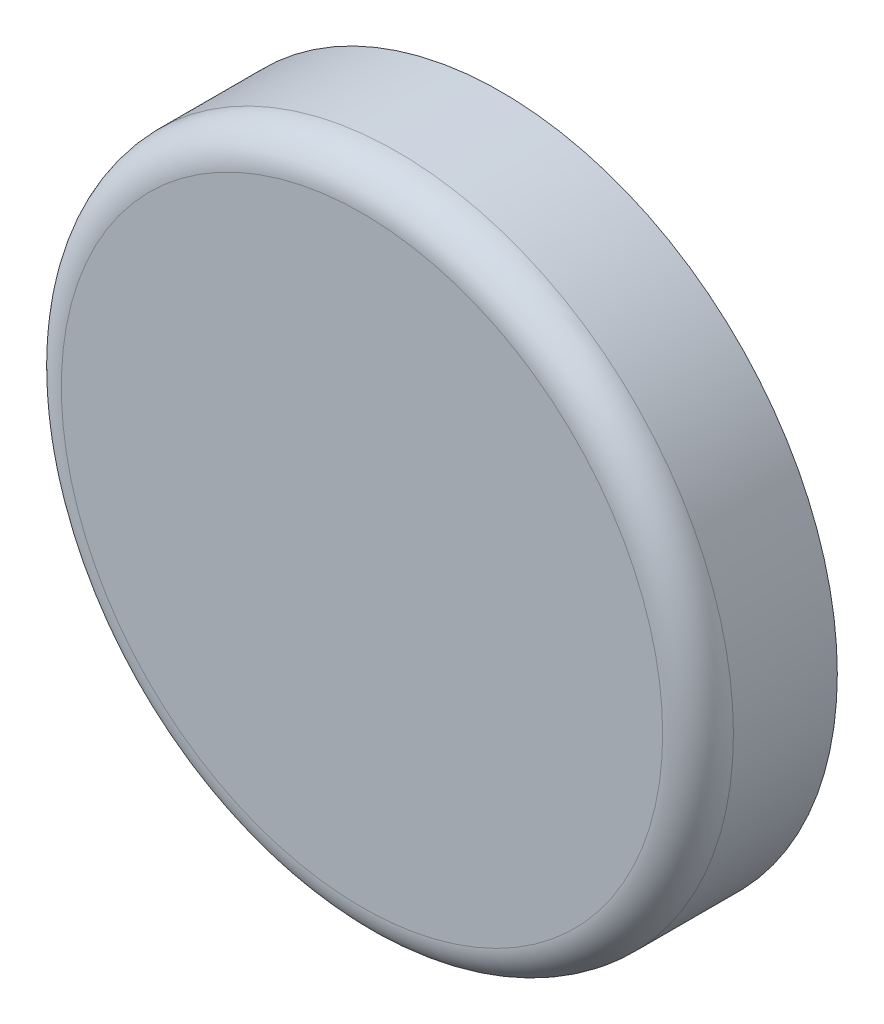
SolidWorks part; units mm, degrees
ref_plane "Front Plane" through (0, 0, 0) normal (0, 0, 1) x (1, 0, 0)
ref_plane "Top Plane" through (0, 0, 0) normal (0, 1, 0) x (1, 0, 0)
ref_plane "Right Plane" through (0, 0, 0) normal (1, 0, 0) x (0, 0, -1)
sketch "Sketch1" plane through (0, 0, 0) normal (0, 0, 1) x (1, 0, 0)
  circle A0 centre (0, 0) radius 12.065
  dimension "D1" = 24.13
extrude "Boss-Extrude1" add sketch "Sketch1" along normal blind 5
fillet "Fillet1" radius 1.27 1 edges at (12.065, 0, 5)
sketch "Sketch2" plane through (0, 0, 0) normal (0, 0, -1) x (-1, 0, 0)
  line L0 (0, 12.065) -> (0, -12.065) construction
  line L1 (-3.1, -3.1) -> (3.1, -3.1) construction
  line L2 (-3.1, -3.1) -> (-3.1, 3.1) construction
  line L3 (-3.1, 3.1) -> (3.1, 3.1) construction
  line L4 (3.1, -3.1) -> (3.1, 3.1) construction
  line L5 (-3.1, -3.1) -> (3.1, 3.1) construction
  line L6 (-3.1, 3.1) -> (3.1, -3.1) construction
  line L7 (-12.065, 0) -> (12.065, 0) construction
  line L8 (3.1, 2.084) -> (4.116, 2.084)
  line L9 (-2.084, 3.1) -> (2.084, 3.1)
  line L10 (-2.084, 3.1) -> (-2.084, 4.116)
  line L11 (-2.084, 4.116) -> (2.084, 4.116)
  line L12 (2.084, 3.1) -> (2.084, 4.116)
  line L13 (3.1, 2.084) -> (3.1, -2.084)
  line L14 (3.1, -2.084) -> (4.116, -2.084)
  line L15 (4.116, 2.084) -> (4.116, -2.084)
  line L16 (2.084, -3.1) -> (2.084, -4.116)
  line L17 (2.084, -3.1) -> (-2.084, -3.1)
  line L18 (-2.084, -3.1) -> (-2.084, -4.116)
  line L19 (2.084, -4.116) -> (-2.084, -4.116)
  line L20 (-3.1, -2.084) -> (-4.116, -2.084)
  line L21 (-3.1, -2.084) -> (-3.1, 2.084)
  line L22 (-3.1, 2.084) -> (-4.116, 2.084)
  line L23 (-4.116, -2.084) -> (-4.116, 2.084)
  circle A0 centre (0, 0) radius 12.065 construction
  point P0 (0, 0)
  point P18 (0, 4.116)
  point P33 (0, 0)
  dimension "D2" = 6.2
  dimension "D3" = 1.016
  dimension "D4" = 1.016
  dimension "D5" = 4
extrude "Boss-Extrude2" add sketch "Sketch2" along normal blind 1.524
